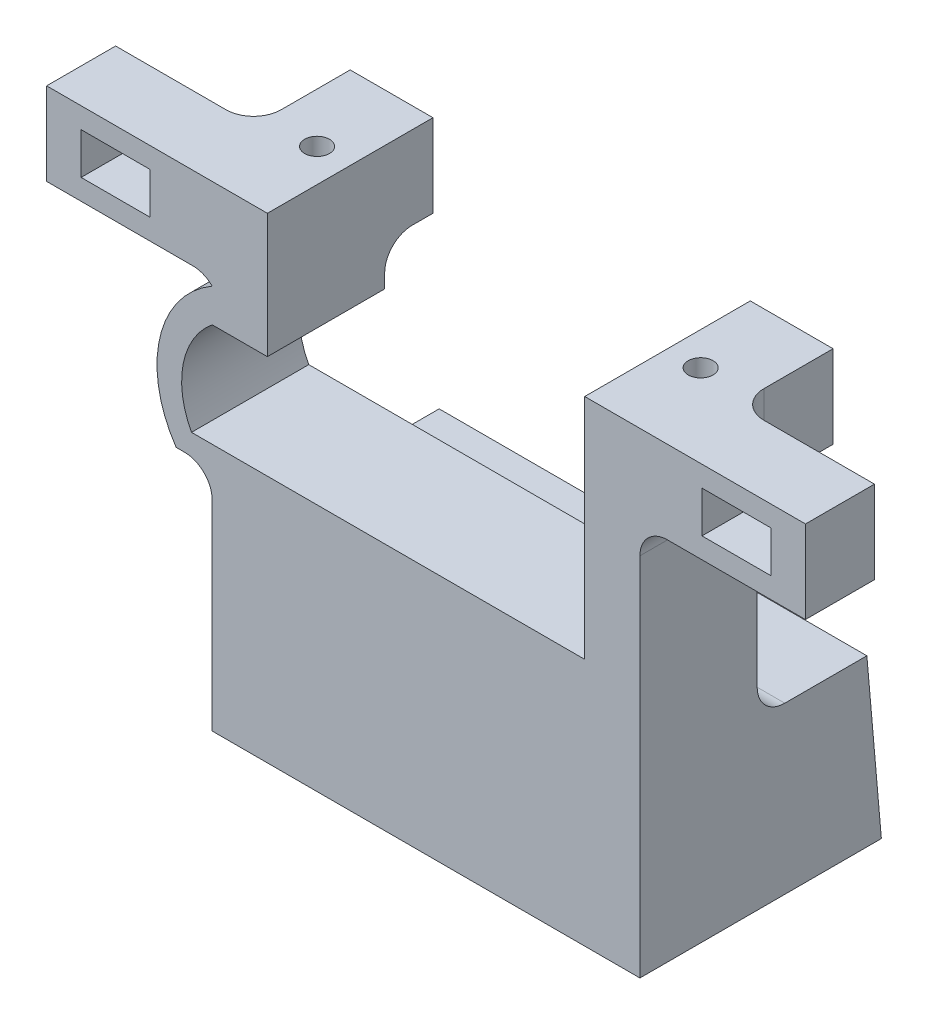
SolidWorks part; units mm, degrees
ref_plane "Front Plane" through (0, 0, 0) normal (0, 0, 1) x (1, 0, 0)
ref_plane "Top Plane" through (0, 0, 0) normal (0, 1, 0) x (1, 0, 0)
ref_plane "Right Plane" through (0, 0, 0) normal (1, 0, 0) x (0, 0, -1)
sketch "Sketch1" plane through (0, 0, 0) normal (0, 1, 0) x (1, 0, 0)
  line L0 (-11.5, 0) -> (11.5, 0) construction
  line L1 (-17.5, 6) -> (-11.5, 6)
  line L2 (-17.5, 6) -> (-17.5, -6)
  line L3 (-17.5, -6) -> (-11.5, -6)
  line L4 (-11.5, 6) -> (-11.5, -6)
  line L5 (11.5, 6) -> (17.5, 6)
  line L6 (11.5, 6) -> (11.5, -6)
  line L7 (11.5, -6) -> (17.5, -6)
  line L8 (17.5, 6) -> (17.5, -6)
  circle A0 centre (-13.9, 0) radius 0.9
  circle A1 centre (13.9, 0) radius 0.9
  dimension "D4" = 27.8
  dimension "D5" = 1.8
  dimension "D6" = 2.4
  dimension "D1" = 12
  dimension "D2" = 23
  dimension "D3" = 6
extrude "Servo Mounting Base" add sketch "Sketch1" along normal blind 6
sketch "Sketch2" plane through (0, 0, 0) normal (0, 0, 1) x (1, 0, 0)
  line L0 (-15.5, 0) -> (-15.5, -28.5)
  line L1 (-17.5, 0) -> (-11.5, 0) construction
  line L2 (-15.5, -28.5) -> (15.5, -28.5)
  line L3 (-15.5, 0) -> (-11.5, 0)
  line L4 (-11.5, 0) -> (-11.5, -10.5)
  line L5 (-11.5, -10.5) -> (11.5, -10.5)
  line L6 (-17.5, 6) -> (-11.5, 6) construction
  line L7 (0, 0) -> (0, -28.5) construction
  line L8 (15.5, 0) -> (11.5, 0)
  line L9 (11.5, 0) -> (11.5, -10.5)
  line L10 (15.5, 0) -> (15.5, -28.5)
  point P18 (0, -10.5)
  dimension "D1" = 16.5
  dimension "D2" = 18
  dimension "D3" = 4
extrude "Servo Enclosing Frame" add sketch "Sketch2" along normal mid plane 5
sketch "Sketch6" plane through (0, 0, 0) normal (0, 0, 1) x (1, 0, 0)
  line L0 (-11.5, -10.5) -> (-11.5, 0) construction
  line L2 (-11.5, -3) -> (-11.5, -12)
  line L3 (11.5, -10.5) -> (-11.5, -10.5) construction
  line L4 (-11.5, -3) -> (-15.5, -3)
  line L5 (-15.5, 0) -> (-15.5, -28.5) construction
  line L6 (-15.5, -3) -> (-15.5, -12)
  line L7 (-15.5, -12) -> (-11.5, -12)
  dimension "D1" = 7.5
  dimension "D2" = 1.5
extrude "Wire Slot" cut sketch "Sketch6" against normal through all both and the other way through all
sketch "Sketch7" plane through (0, 0, 0) normal (0, 0, 1) x (1, 0, 0)
  line L0 (-15.5, 0) -> (-15.5, -3) construction
  line L3 (-11.5, -10.5) -> (-11.5, -12) construction
  line L4 (-11.5, -3) -> (-11.5, -10.5) construction
  line L5 (-11.5, -12) -> (-18.1144, -12)
  line L6 (-11.5, -10.5) -> (-17, -10.5)
  line L7 (-15.5, -0.5718) -> (-15.5, -3)
  line L8 (-15.5, 0) -> (-15.5, -3) construction
  line L9 (-15.5, -12) -> (-15.5, -28.5) construction
  line L10 (-15.5, -3) -> (-11.5, -3) construction
  line L11 (-11.5, -12) -> (-15.5, -12) construction
  line L12 (-11.5, -12) -> (-11.5, -10.5)
  arc A0 (-18.1144, -12) -> (-15.5, -0.5718) centre (-11.5, -7.5) cw
  arc A3 (-15.5, -3) -> (-17, -10.5) centre (-11.7165, -7.6567) ccw
  dimension "D1" = 8
  dimension "D2" = 6
  dimension "D3" = 4.5
  dimension "D4" = 1.5
extrude "Wire Compensation" add sketch "Sketch7" along normal mid plane 5
sketch "Sketch9" plane through (-15.5, 0, 0) normal (-1, 0, 0) x (0, 0, 1)
  line L0 (-2.5, -28.5) -> (-11.5, -28.5)
  line L1 (-11.5, -28.5) -> (-10.4501, -16.5)
  line L2 (-10.4501, -16.5) -> (-2.5, -16.5)
  line L4 (-2.5, -16.5) -> (-2.5, -28.5)
  dimension "D1" = 85
  dimension "D2" = 9
  dimension "D3" = 12
extrude "Clamp Extension" add sketch "Sketch9" against normal up to surface (31 mm away) up to face at (15.5, -14.25, 0)
sketch "Sketch12" plane through (0, 0.782, -8.9382) normal (0, 0.0872, -0.9962) x (-1, 0, 0)
  line L0 (0, -16.8938) -> (0, -29.3938)
  line L2 (-15.5, -29.3938) -> (15.5, -29.3938) construction
  line L3 (0, -29.3938) -> (-1.9, -29.3938)
  line L4 (-1.9, -29.3938) -> (-1.9, -16.8938)
  line L5 (-1.9, -16.8938) -> (0, -16.8938)
  dimension "D1" = 1.9
  dimension "D2" = 12.5
revolve "Wire Groove" cut sketch "Sketch12" angle 360 about L0
sketch "Sketch13" plane through (0, 0.782, -8.9382) normal (0, 0.0872, -0.9962) x (-1, 0, 0)
  line L0 (-15.5, -23.3709) -> (15.5, -23.3709) construction
  line L1 (-15.5, -29.3938) -> (-15.5, -17.348) construction
  line L2 (15.5, -17.348) -> (15.5, -29.3938) construction
  line L3 (0, 0) -> (0, -29.5601) construction
  circle A0 centre (-8.5, -23.3709) radius 1.375
  circle A1 centre (8.5, -23.3709) radius 1.375
  ellipse E0 centre (0, -29.3938) end of major axis (-1.9, -29.3938) minor radius 0.1662 (-1.9, -29.3938) -> (1.9, -29.3938) ccw construction
  dimension "D1" = 2.75
  dimension "D2" = 7
extrude "Clamp Screw Holes" cut sketch "Sketch13" against normal blind 6
sketch "Sketch15" plane through (0, 6, 0) normal (0, 1, 0) x (1, 0, 0)
  line L0 (-22.5, -1) -> (-22.5, -6) construction
  line L1 (-17.5, -1) -> (-27.5, -1)
  line L2 (-17.5, -1) -> (-17.5, -6)
  line L3 (-17.5, -6) -> (-27.5, -6)
  line L4 (-27.5, -1) -> (-27.5, -6)
  line L5 (0, 0) -> (0, 8.5429) construction
  line L11 (-17.5, -6) -> (-11.5, -6) construction
  line L12 (17.5, -6) -> (27.5, -6)
  line L13 (27.5, -1) -> (27.5, -6)
  line L14 (17.5, -1) -> (27.5, -1)
  line L15 (17.5, -1) -> (17.5, -6)
  line L20 (-17.5, 6) -> (-17.5, -6) construction
  ellipse E0 centre (0, 10.4501) end of major axis (0, 8.5429) minor radius 1.9 (-1.9, 10.4501) -> (1.9, 10.4501) ccw construction
  point P7 (-22.5, -3.5)
  dimension "D1" = 10
  dimension "D2" = 5
extrude "Ziptie Flaps" add sketch "Sketch15" against normal blind 6
sketch "Sketch17" plane through (0, 0, 6) normal (0, 0, 1) x (1, 0, 0)
  line L1 (-25, 4.5) -> (-20, 4.5)
  line L2 (-25, 4.5) -> (-25, 1.5)
  line L3 (-25, 1.5) -> (-20, 1.5)
  line L4 (-20, 4.5) -> (-20, 1.5)
  line L7 (0, 0) -> (0, -10.5) construction
  line L8 (11.5, -10.5) -> (-17, -10.5) construction
  line L9 (-27.5, 0) -> (-27.5, 6) construction
  line L10 (25, 1.5) -> (20, 1.5)
  line L11 (20, 4.5) -> (20, 1.5)
  line L12 (25, 4.5) -> (20, 4.5)
  line L13 (25, 4.5) -> (25, 1.5)
  point P18 (-27.5, 3)
  point P19 (-25, 3)
  dimension "D1" = 3
  dimension "D2" = 5
  dimension "D3" = 2.5
extrude "Ziptie Holes" cut sketch "Sketch17" against normal up to next
sketch "Sketch16" plane through (0, 0, 2.5) normal (0, 0, 1) x (1, 0, 0)
  line L0 (-15.5, 0) -> (-15.5, -0.5718)
  line L1 (-15.5, 0) -> (-11.5, 0)
  line L2 (-11.5, 0) -> (-11.5, -3)
  line L3 (-11.5, -3) -> (-11.5, 0) construction
  line L4 (-11.5, -3) -> (-15.5, -3)
  line L5 (-17, -10.5) -> (11.5, -10.5)
  line L6 (11.5, 0) -> (11.5, -10.5) construction
  line L7 (11.5, -10.5) -> (-17, -10.5) construction
  line L8 (11.5, -10.5) -> (11.5, 0)
  line L9 (11.5, 0) -> (15.5, 0)
  line L10 (11.5, 0) -> (27.5, 0) construction
  line L11 (15.5, 0) -> (15.5, -28.5)
  line L12 (15.5, -28.5) -> (-15.5, -28.5)
  line L13 (-15.5, -28.5) -> (-15.5, -12)
  line L14 (-15.5, -12) -> (-18.1144, -12)
  arc A0 (-18.1144, -12) -> (-15.5, -0.5718) centre (-11.5, -7.5) cw
  arc A1 (-17, -10.5) -> (-15.5, -3) centre (-11.7165, -7.6567) cw
  arc A2 (-15.5, -3) -> (-17, -10.5) centre (-11.7165, -7.6567) ccw construction
  arc A3 (-15.5, -0.5718) -> (-18.1144, -12) centre (-11.5, -7.5) ccw construction
extrude "Front Extension" add sketch "Sketch16" along normal up to surface (3.5 mm away) up to face at (-22.5, 3, 6)
fillet "2mm Fillets" radius 2 7 edges at (-15.5, -12, 1.75) (-15.5, 0, 1.75) (-13.5, 0, -2.5) (13.5, 0, -2.5) (15.5, 0, 1.75) (-17.5, 3, 1) (0, -16.5, -2.5)
fillet "More 2mm Fillets" radius 2 1 edges at (17.5, 3, 1)
